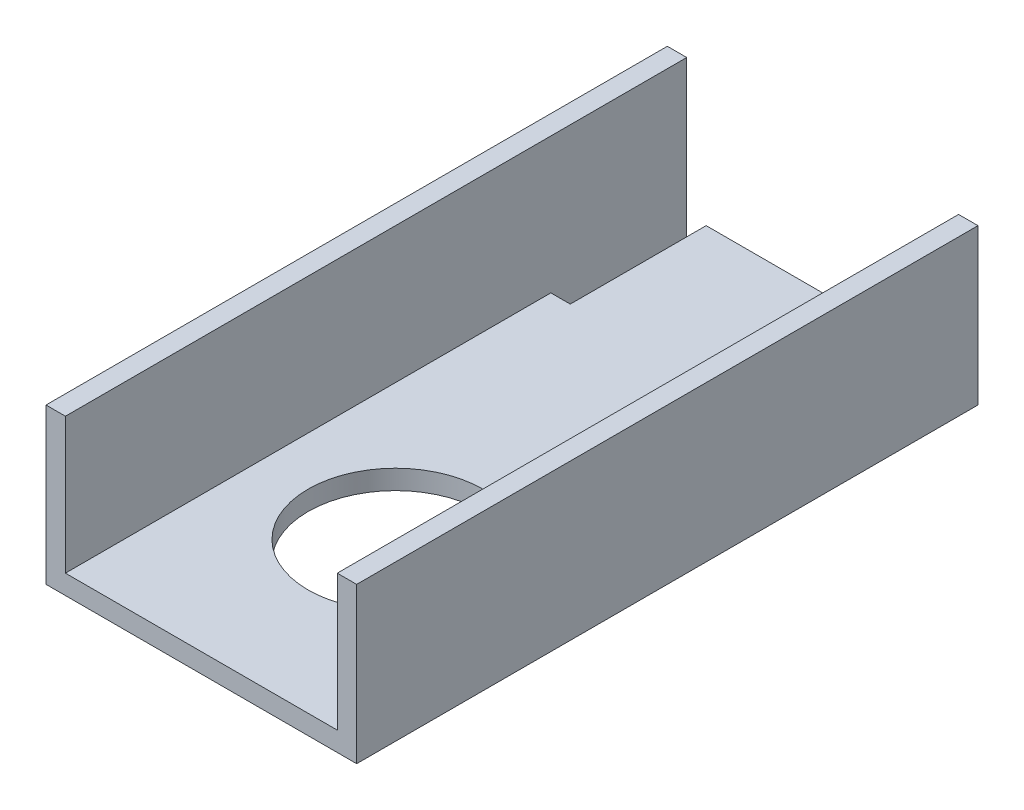
SolidWorks part; units mm, degrees
material "6063-T6"
ref_plane "Front" through (0, 0, 0) normal (0, 0, 1) x (1, 0, 0)
ref_plane "Top" through (0, 0, 0) normal (0, 1, 0) x (1, 0, 0)
ref_plane "Right" through (0, 0, 0) normal (1, 0, 0) x (0, 0, -1)
sketch "Sketch1" plane through (0, 0, 0) normal (0, 0, 1) x (1, 0, 0)
  line L0 (47.625, 3.175) -> (47.625, 25.4)
  line L1 (0, 0) -> (50.8, 0)
  line L2 (0, 0) -> (0, 25.4)
  line L4 (50.8, 0) -> (50.8, 25.4)
  line L5 (3.175, 3.175) -> (47.625, 3.175)
  line L6 (3.175, 3.175) -> (3.175, 25.4)
  line L7 (50.8, 25.4) -> (47.625, 25.4)
  line L8 (0, 25.4) -> (3.175, 25.4)
  dimension "D1" = 25.4
  dimension "D2" = 50.8
  dimension "D3" = 3.175
extrude "Boss-Extrude1" add sketch "Sketch1" along normal blind 101.6
sketch "Sketch2" plane through (0, 0, 0) normal (0, -1, 0) x (1, 0, 0)
  line L0 (25.4, 69.85) -> (25.4, 101.6) construction
  line L1 (0, 101.6) -> (50.8, 101.6) construction
  circle A0 centre (25.4, 69.85) radius 14.2875
  dimension "D1" = 28.575
  dimension "D2" = 31.75
extrude "Cut-Extrude1" cut sketch "Sketch2" against normal up to next
sketch "Sketch3" plane through (0, 3.175, 0) normal (0, 1, 0) x (1, 0, 0)
  line L0 (3.175, -101.6) -> (3.175, 0) construction
  line L1 (3.175, -22.225) -> (6.35, -22.225)
  line L2 (3.175, -22.225) -> (3.175, 0)
  line L3 (3.175, 0) -> (6.35, 0)
  line L4 (6.35, -22.225) -> (6.35, 0)
  line L5 (3.175, -22.225) -> (6.35, 0) construction
  line L6 (3.175, 0) -> (6.35, -22.225) construction
  point P4 (4.7625, -11.1125)
  dimension "D1" = 22.225
  dimension "D2" = 3.175
extrude "Cut-Extrude2" cut sketch "Sketch3" against normal up to next
